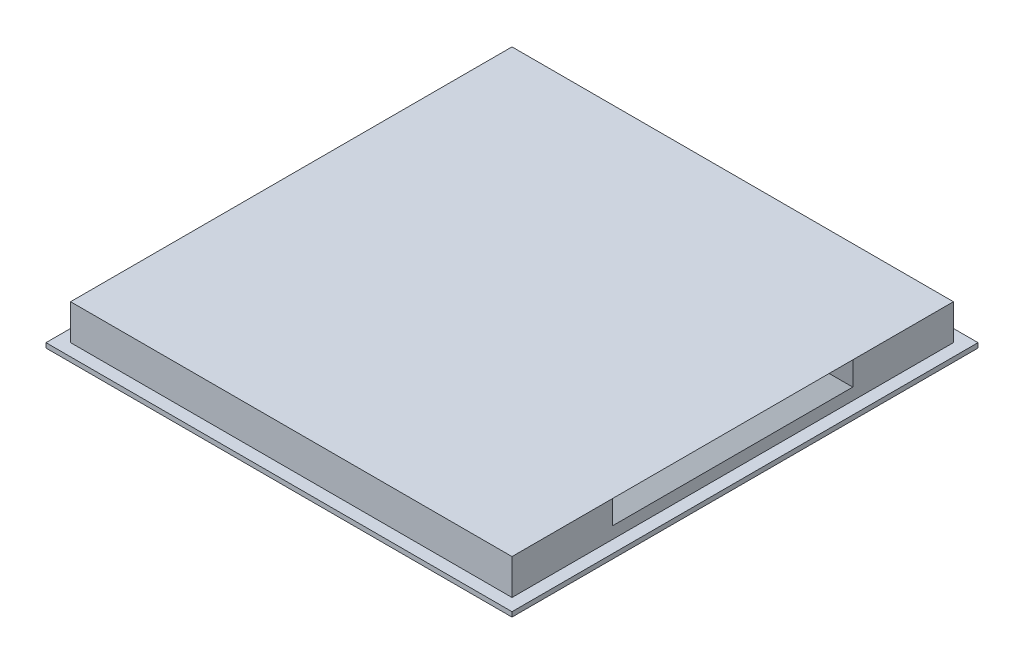
SolidWorks part; units mm, degrees
ref_plane "Front Plane" through (0, 0, 0) normal (0, 0, 1) x (1, 0, 0)
ref_plane "Top Plane" through (0, 0, 0) normal (0, 1, 0) x (1, 0, 0)
ref_plane "Right Plane" through (0, 0, 0) normal (1, 0, 0) x (0, 0, -1)
sketch "Sketch1" plane through (0, 0, 0) normal (0, 1, 0) x (1, 0, 0)
  line L1 (-103.0939, 58.2477) -> (94.1061, 58.2477)
  line L2 (-103.0939, 58.2477) -> (-103.0939, -138.9523)
  line L3 (-103.0939, -138.9523) -> (94.1061, -138.9523)
  line L4 (94.1061, 58.2477) -> (94.1061, -138.9523)
  line L5 (-4.4939, -138.9523) -> (-4.4939, 58.2477) construction
  line L6 (-103.0939, -40.3523) -> (94.1061, -40.3523) construction
  point P68 (-4.4939, -40.3523)
  dimension "D1" = 197.2
  dimension "D2" = 197.2
extrude "Boss-Extrude1" add sketch "Sketch1" along normal blind 2
sketch "Sketch2" plane through (0, 2, 0) normal (0, 1, 0) x (1, 0, 0)
  line L0 (94.1061, -40.3523) -> (88.9061, -40.3523) construction
  line L1 (-97.8939, 53.0477) -> (88.9061, 53.0477)
  line L2 (-97.8939, 53.0477) -> (-97.8939, -133.7523)
  line L3 (-97.8939, -133.7523) -> (88.9061, -133.7523)
  line L4 (88.9061, 53.0477) -> (88.9061, -133.7523)
  line L5 (-4.4939, -133.7523) -> (-4.4939, 53.0477) construction
  line L6 (-97.8939, -40.3523) -> (88.9061, -40.3523) construction
  line L8 (88.9061, -40.3523) -> (-97.8939, -40.3523) construction
  line L9 (-97.8939, -40.3523) -> (-103.0939, -40.3523) construction
  line L10 (-103.0939, 58.2477) -> (-103.0939, -138.9523) construction
  line L11 (-4.4939, 58.2477) -> (-4.4939, 53.0477) construction
  line L12 (94.1061, 58.2477) -> (-103.0939, 58.2477) construction
  line L13 (-4.4939, 53.0477) -> (-4.4939, -133.7523) construction
  line L14 (-4.4939, -133.7523) -> (-4.4939, -138.9523) construction
  line L15 (-103.0939, -138.9523) -> (94.1061, -138.9523) construction
  point P312 (-4.4939, -40.3523)
  dimension "D1" = 5.2
  dimension "D2" = 5.2
  dimension "D3" = 5.2
extrude "Boss-Extrude2" add sketch "Sketch2" along normal blind 15
sketch "Sketch3" plane through (-97.8939, 0, 0) normal (-1, 0, 0) x (0, 0, 1)
  line L0 (-53.0477, 17) -> (133.7523, 17) construction
  line L1 (-10.4477, 17) -> (91.1523, 17)
  line L2 (-10.4477, 17) -> (-10.4477, 7)
  line L3 (-10.4477, 7) -> (91.1523, 7)
  line L4 (91.1523, 17) -> (91.1523, 7)
  line L5 (40.3523, 7) -> (40.3523, 17) construction
  line L6 (-10.4477, 12) -> (91.1523, 12) construction
  point P6 (40.3523, 17)
  point P248 (40.3523, 12)
  dimension "D1" = 10
  dimension "D2" = 101.6
extrude "Cut-Extrude1" cut sketch "Sketch3" against normal blind 6 draft 45
ref_plane "Plane1" through (-4.4939, 0, 0) normal (-1, 0, 0) x (0, 0, 1)
mirror "Mirror1" about plane through (-4.4939, 0, 0) normal (-1, 0, 0) of "Cut-Extrude1"
